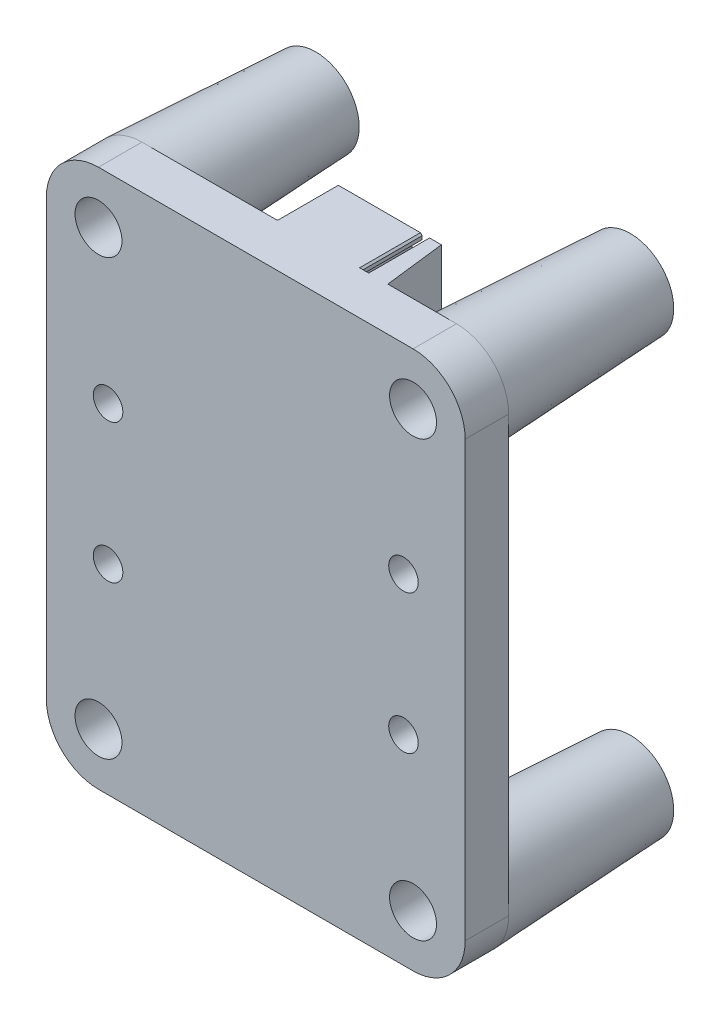
SolidWorks part; units mm, degrees
ref_plane "前视基准面" through (0, 0, 0) normal (0, 0, 1) x (1, 0, 0)
ref_plane "上视基准面" through (0, 0, 0) normal (0, 1, 0) x (1, 0, 0)
ref_plane "右视基准面" through (0, 0, 0) normal (1, 0, 0) x (0, 0, -1)
sketch "草图1" plane through (0, 0, 0) normal (0, 0, 1) x (1, 0, 0)
  line L0 (-612.4365, 0) -> (30009.3904, 0) construction
  line L1 (-611.4109, 10) -> (30010.416, 10) construction
  line L2 (-607.9921, -10) -> (30013.8348, -10) construction
  line L3 (0, -612.4365) -> (0, 30009.3904) construction
  line L4 (-10, -612.4365) -> (-10, 30009.3904) construction
  line L5 (10, -614.6741) -> (10, 30007.1528) construction
  line L6 (-24.1, 25) -> (-24.1, -25)
  line L7 (-14.8035, -30.0133) -> (21.9459, -5.8489) construction
  line L8 (-14.8035, 30.0133) -> (21.9459, 5.8489) construction
  line L9 (-18.1, 31) -> (18.1, 31)
  line L10 (24.1, 25) -> (24.1, -25)
  line L11 (18.1, -31) -> (-18.1, -31)
  circle A0 centre (18.1, 25) radius 11.5 construction
  circle A1 centre (-18.1, 25) radius 11.5 construction
  circle A2 centre (-18.1, -25) radius 11.5 construction
  circle A3 centre (18.1, 0) radius 11.5 construction
  circle A4 centre (18.1, 0) radius 3.5 construction
  circle A5 centre (-18.1, 25) radius 6
  circle A6 centre (17, 8) radius 1.7
  arc A7 (21.9459, -5.8489) -> (21.9459, 5.8489) centre (18.1, 0) ccw construction
  circle A8 centre (-18.1, 25) radius 2.7
  circle A9 centre (-18.1, -25) radius 2.7
  circle A10 centre (-18.1, 25) radius 5 construction
  circle A11 centre (-18.1, -25) radius 5 construction
  circle A12 centre (18.1, 0) radius 5 construction
  circle A13 centre (18.1, 0) radius 7 construction
  circle A14 centre (-17, 8) radius 1.7
  circle A15 centre (-18.1, -25) radius 6
  circle A16 centre (17, -8) radius 1.7
  circle A17 centre (-17, -8) radius 1.7
  circle A20 centre (18.1, -25) radius 6
  circle A21 centre (18.1, -25) radius 5 construction
  circle A22 centre (18.1, -25) radius 2.7
  circle A23 centre (18.1, 25) radius 6
  circle A24 centre (18.1, 25) radius 5 construction
  circle A25 centre (18.1, 25) radius 2.7
  dimension "D5" = 23
  dimension "D6" = 25
  dimension "D7" = 7
  dimension "D9" = 12
  dimension "D10" = 7
  dimension "D11" = 5.4
  dimension "D12" = 10
  dimension "D8" = 3.4
  dimension "D1" = 20
  dimension "D2" = 10
  dimension "D3" = 20
  dimension "D4" = 10
  dimension "D13" = 18.1
  dimension "D14" = 34
  dimension "D15" = 16
  dimension "D16" = 36.2
extrude "凸台-拉伸1" add sketch "草图1" along normal blind 5 contours A15 L7 A7 L8 A5 L6 A4 | A15 A9 | A5 A8 | A20 A22 | A23 A25 region at (0, 0, 0) region at (-22.2226, 29.1226, 0) region at (-18.1, -19.1697, 0) region at (22.2226, 29.1226, 0) region at (13.9774, -20.8774, 0)
ref_axis "基准轴1" through (-18.1, 25, 5) along (0, 0, -1)
ref_plane "基准面2" through (0, 25, 0) normal (0, 1, 0) x (0, 0, -1)
sketch "草图4" plane through (0, 25, 0) normal (0, 1, 0) x (0, 0, -1)
  line L0 (-1000.279, 18.1) -> (48999.721, 18.1) construction
  line L1 (20, 20.8) -> (26.5, 20.8)
  line L2 (-5, 18.1) -> (0, 18.1) construction
  line L3 (20, 23.1) -> (0, 24.1)
  line L4 (0, 24.1) -> (0, 20.8)
  line L5 (26.5, 20.8) -> (26.5, 26.35)
  line L6 (0, 20.8) -> (20, 20.8)
  line L7 (20, 20.8) -> (20, 23.1) construction
  line L8 (20, 23.1) -> (20, 26.35)
  line L9 (-985.3818, 29.6) -> (49014.6182, 29.6) construction
  line L10 (13.25, -1000.5381) -> (13.25, 48999.4619) construction
  line L13 (33.25, -999.9203) -> (33.25, 49000.0797) construction
  line L14 (23.25, -1000.2466) -> (23.25, 48999.7534) construction
  line L15 (20, 23.1) -> (20, 20.8)
  arc A0 (26.5, 26.35) -> (20, 26.35) centre (23.25, 26.35) ccw
  point P7 (0, 0)
  dimension "D5" = 11.5
  dimension "D1" = 2.7
  dimension "D2" = 5
  dimension "D3" = 20
  dimension "D4" = 10
  dimension "D6" = 6.5
  dimension "D7" = 20
  dimension "D11" = 13.25
revolve "旋转1" add sketch "草图4" angle 360 about L0 region at (-22.2149, 25, -9.4048)
mirror "镜向1" about plane through (0, 0, 0) normal (0, 1, 0) of "旋转1"
mirror "镜向2" about plane through (0, 0, 0) normal (1, 0, 0) of "镜向1", "旋转1"
sketch "草图5" plane through (0, 0, 5) normal (0, 0, 1) x (1, 0, 0)
  line L0 (0, -1000) -> (0, 49000) construction
  line L1 (-6, -1003.6795) -> (-6, 48996.3205) construction
  line L2 (8, -1003.2098) -> (8, 0.5) construction
  line L3 (8, 31) -> (8, 15)
  line L4 (-18.1, 31) -> (18.1, 31) construction
  line L5 (8, 15) -> (9, 15)
  line L6 (9, 15) -> (9, 31)
  line L7 (9, 31) -> (8, 31)
  line L8 (6, 31) -> (6, 15) construction
  line L9 (6, 15) -> (2.4, 15)
  line L10 (2.4, 15) -> (2.4, 31) construction
  line L11 (2.4, 31) -> (6, 31)
  line L12 (-2.5, 31) -> (-2.5, 15)
  line L13 (-2.5, 15) -> (0.4, 15)
  line L14 (0.4, 15) -> (0.4, 31)
  line L15 (0.4, 31) -> (-2.5, 31)
  line L16 (0.4, 15) -> (2.4, 15) construction
  line L17 (6, 15) -> (8, 15) construction
  line L18 (-1000, 0) -> (49000, 0) construction
  line L19 (8, -31) -> (9, -31)
  line L20 (18.1, -31) -> (-18.1, -31) construction
  line L21 (9, -31) -> (9, 0.5)
  line L22 (9, 0.5) -> (8, 0.5)
  line L23 (8, 0.5) -> (8, -31)
  line L24 (6, -31) -> (6, -24.5)
  line L25 (6, -24.5) -> (-1, -24.5)
  line L26 (-2.5, -24.5) -> (-2.5, -31)
  line L27 (-2.5, -31) -> (6, -31)
  line L28 (-1, -24.5) -> (-1, -0.5)
  line L29 (-1, -26.1) -> (5, -26.1)
  line L30 (-1, -26.1) -> (-1, -29)
  line L31 (-1, -29) -> (5, -29)
  line L32 (5, -26.1) -> (5, -29)
  line L33 (-1, 0.5) -> (-2.5, 0.5)
  line L34 (-2.5, 0.5) -> (-2.5, -24.5)
  line L35 (-1, 0.5) -> (6, 0.5)
  line L36 (-1, -0.5) -> (6, -0.5)
  line L37 (6, -0.5) -> (6, 0.5)
  line L38 (6, 31) -> (6.95, 31)
  line L39 (6.95, 31) -> (7.15, 30.8)
  line L40 (7.15, 30.8) -> (7.15, 30.4)
  line L41 (7.15, 30.4) -> (6.95, 30.2)
  line L42 (6.95, 30.2) -> (6, 30.2)
  line L43 (6, 30.2) -> (6, 29)
  line L44 (4.2, 31) -> (4.2, 15) construction
  line L45 (2.4, 31) -> (1.45, 31)
  line L46 (1.45, 31) -> (1.25, 30.8)
  line L47 (1.25, 30.4) -> (1.45, 30.2)
  line L48 (1.25, 30.8) -> (1.25, 30.4)
  line L49 (1.45, 30.2) -> (2.4, 30.2)
  line L50 (2.4, 30.2) -> (2.4, 29)
  line L51 (2.4, 28.2) -> (2.4, 27)
  line L52 (1.45, 28.2) -> (2.4, 28.2)
  line L53 (1.25, 28.4) -> (1.45, 28.2)
  line L54 (1.25, 28.8) -> (1.25, 28.4)
  line L55 (1.45, 29) -> (1.25, 28.8)
  line L56 (2.4, 29) -> (1.45, 29)
  line L57 (6, 28.2) -> (6, 27)
  line L58 (6.95, 28.2) -> (6, 28.2)
  line L59 (7.15, 28.4) -> (6.95, 28.2)
  line L60 (7.15, 28.8) -> (7.15, 28.4)
  line L61 (6.95, 29) -> (7.15, 28.8)
  line L62 (6, 29) -> (6.95, 29)
  line L63 (2.4, 26.2) -> (2.4, 25)
  line L64 (1.45, 26.2) -> (2.4, 26.2)
  line L65 (1.25, 26.4) -> (1.45, 26.2)
  line L66 (1.25, 26.8) -> (1.25, 26.4)
  line L67 (1.45, 27) -> (1.25, 26.8)
  line L68 (2.4, 27) -> (1.45, 27)
  line L69 (6, 26.2) -> (6, 25)
  line L70 (6.95, 26.2) -> (6, 26.2)
  line L71 (7.15, 26.4) -> (6.95, 26.2)
  line L72 (7.15, 26.8) -> (7.15, 26.4)
  line L73 (6.95, 27) -> (7.15, 26.8)
  line L74 (6, 27) -> (6.95, 27)
  line L75 (2.4, 24.2) -> (2.4, 23)
  line L76 (1.45, 24.2) -> (2.4, 24.2)
  line L77 (1.25, 24.4) -> (1.45, 24.2)
  line L78 (1.25, 24.8) -> (1.25, 24.4)
  line L79 (1.45, 25) -> (1.25, 24.8)
  line L80 (2.4, 25) -> (1.45, 25)
  line L81 (6, 24.2) -> (6, 23)
  line L82 (6.95, 24.2) -> (6, 24.2)
  line L83 (7.15, 24.4) -> (6.95, 24.2)
  line L84 (7.15, 24.8) -> (7.15, 24.4)
  line L85 (6.95, 25) -> (7.15, 24.8)
  line L86 (6, 25) -> (6.95, 25)
  line L87 (2.4, 22.2) -> (2.4, 21)
  line L88 (1.45, 22.2) -> (2.4, 22.2)
  line L89 (1.25, 22.4) -> (1.45, 22.2)
  line L90 (1.25, 22.8) -> (1.25, 22.4)
  line L91 (1.45, 23) -> (1.25, 22.8)
  line L92 (2.4, 23) -> (1.45, 23)
  line L93 (6, 22.2) -> (6, 21)
  line L94 (6.95, 22.2) -> (6, 22.2)
  line L95 (7.15, 22.4) -> (6.95, 22.2)
  line L96 (7.15, 22.8) -> (7.15, 22.4)
  line L97 (6.95, 23) -> (7.15, 22.8)
  line L98 (6, 23) -> (6.95, 23)
  line L99 (2.4, 20.2) -> (2.4, 19)
  line L100 (1.45, 20.2) -> (2.4, 20.2)
  line L101 (1.25, 20.4) -> (1.45, 20.2)
  line L102 (1.25, 20.8) -> (1.25, 20.4)
  line L103 (1.45, 21) -> (1.25, 20.8)
  line L104 (2.4, 21) -> (1.45, 21)
  line L105 (6, 20.2) -> (6, 19)
  line L106 (6.95, 20.2) -> (6, 20.2)
  line L107 (7.15, 20.4) -> (6.95, 20.2)
  line L108 (7.15, 20.8) -> (7.15, 20.4)
  line L109 (6.95, 21) -> (7.15, 20.8)
  line L110 (6, 21) -> (6.95, 21)
  line L111 (2.4, 18.2) -> (2.4, 17)
  line L112 (1.45, 18.2) -> (2.4, 18.2)
  line L113 (1.25, 18.4) -> (1.45, 18.2)
  line L114 (1.25, 18.8) -> (1.25, 18.4)
  line L115 (1.45, 19) -> (1.25, 18.8)
  line L116 (2.4, 19) -> (1.45, 19)
  line L117 (6, 18.2) -> (6, 17)
  line L118 (6.95, 18.2) -> (6, 18.2)
  line L119 (7.15, 18.4) -> (6.95, 18.2)
  line L120 (7.15, 18.8) -> (7.15, 18.4)
  line L121 (6.95, 19) -> (7.15, 18.8)
  line L122 (6, 19) -> (6.95, 19)
  line L123 (2.4, 16.2) -> (2.4, 15)
  line L124 (1.45, 16.2) -> (2.4, 16.2)
  line L125 (1.25, 16.4) -> (1.45, 16.2)
  line L126 (1.25, 16.8) -> (1.25, 16.4)
  line L127 (1.45, 17) -> (1.25, 16.8)
  line L128 (2.4, 17) -> (1.45, 17)
  line L129 (6, 16.2) -> (6, 15)
  line L130 (6.95, 16.2) -> (6, 16.2)
  line L131 (7.15, 16.4) -> (6.95, 16.2)
  line L132 (7.15, 16.8) -> (7.15, 16.4)
  line L133 (6.95, 17) -> (7.15, 16.8)
  line L134 (6, 17) -> (6.95, 17)
  line L135 (24.1, 25) -> (24.1, -25) construction
  line L137 (0.4, 31) -> (2.4, 31)
  line L138 (0.4, 15) -> (2.4, 15)
  circle A0 centre (18.1, 25) radius 2.7 construction
  circle A1 centre (-18.1, 25) radius 2.7 construction
  circle A2 centre (-18.1, -25) radius 2.7 construction
  circle A3 centre (18.1, -25) radius 2.7 construction
  circle A4 centre (18.1, 25) radius 2.7 construction
  circle A5 centre (-18.1, 25) radius 2.7 construction
  circle A6 centre (-18.1, -25) radius 2.7 construction
  circle A7 centre (18.1, -25) radius 2.7 construction
  circle A8 centre (18.1, 25) radius 6 construction
  circle A9 centre (-18.1, 25) radius 6 construction
  circle A10 centre (-18.1, -25) radius 6 construction
  circle A11 centre (18.1, -25) radius 6 construction
  circle A12 centre (14, 9) radius 2.2
  circle A13 centre (14, 9) radius 5
  circle A14 centre (-14, 9) radius 2.2
  circle A15 centre (-14, 9) radius 5
  circle A16 centre (14, -9) radius 2.2
  circle A17 centre (14, -9) radius 5
  circle A18 centre (-14, -9) radius 5
  circle A19 centre (-14, -9) radius 2.2
  line M3 (18.1, 31) -> (-18.1, 31)
  line M7 (-18.1, -31) -> (18.1, -31)
  dimension "D24" = 4.4
  dimension "D25" = 10
  dimension "D1" = 8
  dimension "D2" = 14
  dimension "D3" = 2.9
  dimension "D4" = 1
  dimension "D5" = 2
  dimension "D6" = 3.6
  dimension "D7" = 7
  dimension "D8" = 16
  dimension "D9" = 6
  dimension "D10" = 2.9
  dimension "D11" = 2
  dimension "D12" = 1.6
  dimension "D13" = 1.5
  dimension "D14" = 1
  dimension "D15" = 1
  dimension "D16" = 24
  dimension "D17" = 2
  dimension "D18" = 0.8
  dimension "D19" = 0.85
  dimension "D20" = 0.2
  dimension "D21" = 0.2
  dimension "D22" = 2
  dimension "D26" = 18
  dimension "D27" = 8
  dimension "D23" = 8
extrude "凸台-拉伸2" add sketch "草图5" against normal blind 8 from offset 4 contours L22 L23 L21 M7 | L36 L37 L35 L33 L34 L26 L24 L25 L28 L29 L32 L31 L30 M7 | L134 L117 L118 L119 L120 L121 L122 L105 L106 L107 L108 L109 L110 L93 L94 L95 L96 L97 L98 L81 L82 L83 L84 L85 L86 L69 L70 L71 L72 L73 L74 L57 L58 L59 L60 L61 L62 L43 L42 L41 L40 L39 L46 L48 L47 L49 L50 L56 M3 | L5 L6 L3 M3 | L13 L14 L12 M3 | L14 L138 L123 L124 L125 L126 L127 L128 L111 L112 L113 L114 L115 L116 L99 L100 L101 L102 L103 L104 L87 L88 L89 L90 L91 L92 L75 L76 L77 L78 L79 L80 L63 L64 L65 L66 L67 L68 L51 L52 L53 L54 L55 L56 L50 L49 L47 L48 L46 M3 region at (8.5, 23, 5) region at (4.2, 23.1179, 5) region at (1.2736, 22.8308, 5) region at (-1.05, 23, 5) region at (8.5, -15.25, 5) region at (1.75, -30.6737, 5) offset against normal yes
sketch "草图6" plane through (0, -31, 0) normal (0, -1, 0) x (1, 0, 0)
  line L4 (-1, 0) -> (-1, -7)
  line L5 (-1, 0) -> (-1, -7)
  line L8 (5, 0) -> (-1, 0)
  line L10 (-1, -7) -> (5, -7)
  line L11 (5, -7) -> (5, 0)
  line L12 (5, 0) -> (-1, 0)
  line L14 (-1, -7) -> (5, -7)
  line L15 (5, -7) -> (5, 0)
  circle A0 centre (2, -3.5) radius 1.8
  dimension "D1" = 3.6
  dimension "D2" = 7
  dimension "D3" = 3
  dimension "D5" = 3.5
  dimension "D4" = 0
extrude "切除-拉伸1" cut sketch "草图6" against normal up to surface (6.5 mm away) contours A0 region at (2, -31, -3.5) up to face at (2.5, -24.5, -3.5)
chamfer "倒角1" distance 1.2 distance2 10 2 edges at (9, 23, 0) (1.75, 0.5, 0) first distance on face at (5.1146, 15.0276, 0)
chamfer "倒角2" distance 10 distance2 1.2 2 edges at (9, -15.25, 0) (8.5, 0.5, 0) first distance on face at (9, -15.25, -3.5) first distance on face at (8.5, 0.5, -3.5)
